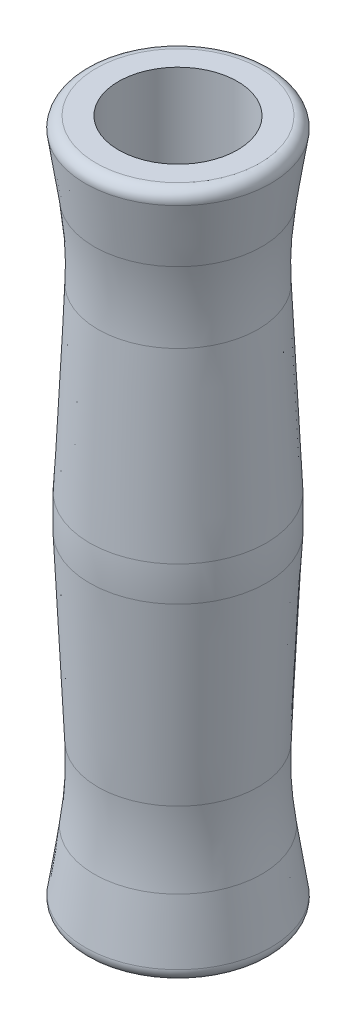
SolidWorks part; units mm, degrees
material "Сосна"
ref_plane "Спереди" through (0, 0, 0) normal (0, 0, 1) x (1, 0, 0)
ref_plane "Сверху" through (0, 0, 0) normal (0, 1, 0) x (1, 0, 0)
ref_plane "Справа" through (0, 0, 0) normal (1, 0, 0) x (0, 0, -1)
sketch "Эскиз1" plane through (0, 0, 0) normal (0, 0, 1) x (1, 0, 0)
  line L0 (0, 0) -> (17.5, 0)
  line L1 (17.5, 0) -> (14.5, -20)
  line L2 (14.5, -20) -> (16.5, -63.5)
  line L3 (0, 24.4253) -> (0, -138.5525) construction
  line L4 (-22.3442, -63.5) -> (25.125, -63.5) construction
  line L5 (0, -127) -> (17.5, -127)
  line L6 (17.5, -127) -> (14.5, -107)
  line L7 (14.5, -107) -> (16.5, -63.5)
  line L8 (0, 0) -> (0, -127)
  dimension "D1" = 17.5
  dimension "D2" = 63.5
  dimension "D3" = 29
  dimension "D4" = 33
  dimension "D5" = 20
revolve "Повернуть1" add sketch "Эскиз1" angle 360 about L3
fillet "Скругление1" radius 2 2 edges at (0, -127, 17.5) (0, 0, 17.5)
fillet "Скругление2" radius 70 3 edges at (0, -107, 14.5) (0, -20, 14.5) (0, -63.5, 16.5)
sketch "Эскиз2" plane through (0, 0, 0) normal (0, 1, 0) x (1, 0, 0)
  circle A0 centre (0, 0) radius 11
  dimension "D1" = 22
extrude "Вырез-Вытянуть1" cut sketch "Эскиз2" against normal through all
